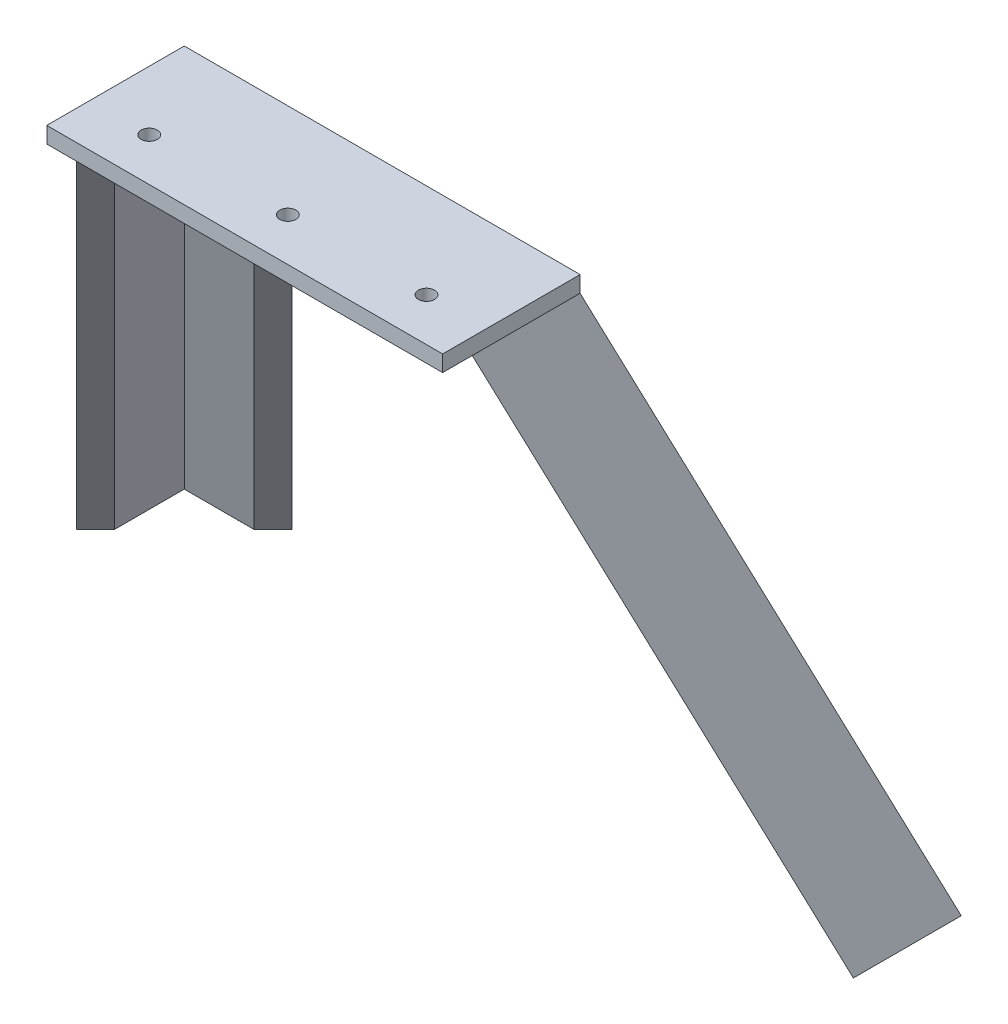
SolidWorks part; units mm, degrees
ref_plane "前视基准面" through (0, 0, 0) normal (0, 0, 1) x (1, 0, 0)
ref_plane "上视基准面" through (0, 0, 0) normal (0, 1, 0) x (1, 0, 0)
ref_plane "右视基准面" through (0, 0, 0) normal (1, 0, 0) x (0, 0, -1)
other "Configuration Table"
ref_plane "基准面2" through (0, 100, 0) normal (0, 1, 0) x (1, 0, 0)
sketch "草图8" plane through (0, 100, 0) normal (0, 1, 0) x (1, 0, 0)
  line L1 (-47.7955, 35.7204) -> (25.6259, 35.7204)
  line L2 (-47.7955, 35.7204) -> (-47.7955, 10.2204)
  line L3 (-47.7955, 10.2204) -> (25.6259, 10.2204)
  line L4 (25.6259, 35.7204) -> (25.6259, 10.2204)
extrude "凸台-拉伸3" add sketch "草图8" along normal blind 3
sketch "草图9" plane through (0, 103, 0) normal (0, 1, 0) x (1, 0, 0)
  circle A0 centre (-36.7955, 18.2204) radius 1.5
  circle A1 centre (14.6259, 18.2204) radius 1.5
  circle A2 centre (-11.0848, 18.2204) radius 1.5
extrude "切除-拉伸2" cut sketch "草图9" against normal blind 3
sketch "草图10" plane through (0, 100, 0) normal (0, 1, 0) x (1, 0, 0)
  line L0 (-47.7955, 35.7204) -> (-27.7955, 35.7204)
  line L1 (25.6259, 35.7204) -> (-47.7955, 35.7204) construction
  line L2 (-47.7955, 35.7204) -> (-47.7955, 15.7204)
  line L3 (-47.7955, 35.7204) -> (-47.7955, 10.2204) construction
  line L4 (-27.7955, 35.7204) -> (-47.7955, 15.7204)
sketch "草图11" plane through (0, 0, 0) normal (0, 1, 0) x (1, 0, 0)
  line L0 (-83.1508, 71.0757) -> (-63.1508, 71.0757)
  line L1 (-63.1508, 71.0757) -> (-83.1508, 51.0757)
  line L2 (-83.1508, 51.0757) -> (-83.1508, 71.0757)
loft "放样2" add profiles "草图10", "草图11" connector at (-27.7955, 100, -35.7204) connector at (-63.1508, 0, -71.0757)
sketch "草图12" plane through (0, 100, 0) normal (0, 1, 0) x (1, 0, 0)
  line L0 (-31.331, 32.1849) -> (-44.2599, 19.2559)
  line L3 (-44.2599, 32.1849) -> (-31.331, 32.1849)
  line L9 (-44.2599, 32.1849) -> (-44.2599, 19.2559)
sketch "草图13" plane through (0, 0, 0) normal (0, 1, 0) x (1, 0, 0)
  line L1 (-47.7955, 35.7204) -> (-83.1508, 71.0757) construction
  line L3 (-66.6863, 67.5402) -> (-79.6153, 54.6113)
  line L4 (-79.6153, 67.5402) -> (-66.6863, 67.5402)
  line L5 (-79.6153, 67.5402) -> (-79.6153, 54.6113)
loft "切除-放样1" cut profiles "草图12", "草图13" connector at (-31.331, 100, -32.1849) connector at (-66.6863, 0, -67.5402)
ref_plane "基准面4" through (-11, 0, 0) normal (1, 0, 0) x (0, 0, -1)
ref_plane "基准面6" through (-11.1, 0, 0) normal (1, 0, 0) x (0, 0, -1)
mirror "镜向3" about plane through (-11.1, 0, 0) normal (1, 0, 0) of "放样2"
mirror "镜向4" about plane through (-11.1, 0, 0) normal (1, 0, 0) of "切除-放样1"
